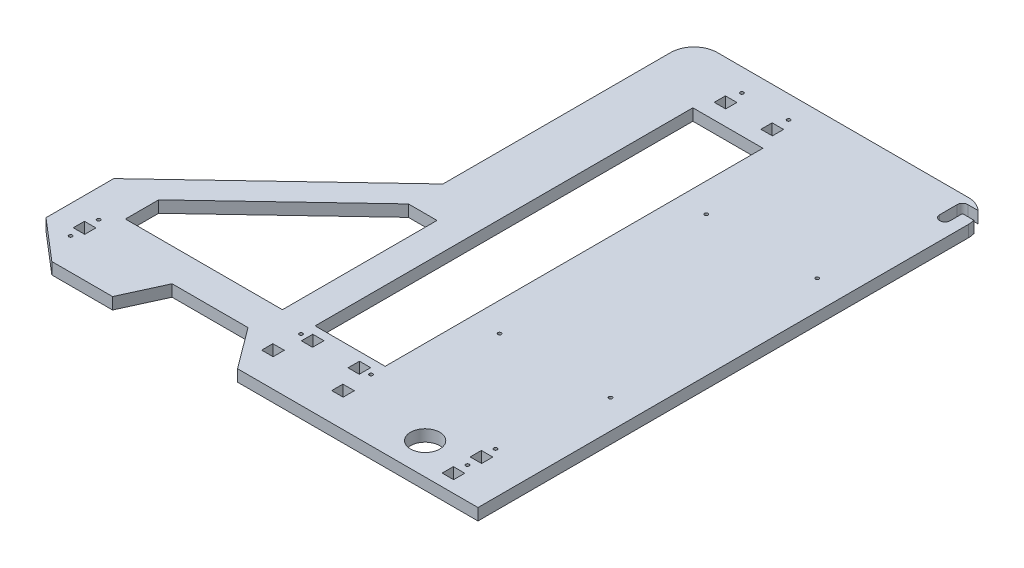
SolidWorks part; units mm, degrees
ref_plane "Front Plane" through (0, 0, 0) normal (0, 0, 1) x (1, 0, 0)
ref_plane "Top Plane" through (0, 0, 0) normal (0, 1, 0) x (1, 0, 0)
ref_plane "Right Plane" through (0, 0, 0) normal (1, 0, 0) x (0, 0, -1)
sketch "Sketch1" plane through (0, 0, 0) normal (0, 1, 0) x (1, 0, 0)
  line L0 (0, 0) -> (-235, 0)
  line L1 (-235, 0) -> (-235, -215)
  line L2 (-235, -215) -> (-380, -352)
  line L3 (-380, -352) -> (-380, -410)
  line L4 (-380, -410) -> (-345, -440)
  line L5 (-345, -440) -> (-293, -440)
  line L6 (-293, -440) -> (-277, -405)
  line L7 (-277, -405) -> (-212, -405)
  line L8 (-212, -405) -> (-185.9255, -440)
  line L9 (-185.9255, -440) -> (0, -440)
  line L10 (0, 0) -> (0, -440)
  line L12 (-293, -440) -> (-185.9255, -440) construction
  dimension "D3" = 235
  dimension "D5" = 58
  dimension "D13" = 190
  dimension "D7" = 35
  dimension "D2" = 126.686
  dimension "D11" = 65
  dimension "D15" = 52
  dimension "D12" = 30
  dimension "D10" = 35
  dimension "D14" = 16
  dimension "D6" = 380
  dimension "D4" = 440
extrude "Boss-Extrude1" add sketch "Sketch1" along normal blind 10
sketch "Sketch16" plane through (0, 10, 0) normal (0, 1, 0) x (1, 0, 0)
  line L0 (0, -440) -> (20, -440)
  line L1 (20, -440) -> (20, 0)
  line L2 (20, 0) -> (0, 0)
  line L3 (0, 0) -> (0, -440)
  dimension "D1" = 20
  dimension "D2" = 90
extrude "Boss-Extrude2" add sketch "Sketch16" against normal through all
sketch "Sketch2" plane through (0, 10, 0) normal (0, 1, 0) x (1, 0, 0)
  line L0 (-235, -215) -> (-235, -405) construction
  line L1 (-277, -405) -> (-212, -405) construction
  line L2 (-345, -440) -> (-345, -318.931) construction
  line L3 (-235, -215) -> (-380, -352) construction
  line L4 (-345, -348.5097) -> (-235, -244.5787)
  line L5 (-235, -244.5787) -> (-210.5, -244.5787)
  line L6 (-210.5, -244.5787) -> (-210.5, -377)
  line L7 (-210.5, -377) -> (-345, -377)
  line L8 (-345, -377) -> (-345, -348.5097)
  line L9 (0, -440) -> (0, 0) construction
  line L10 (-184.5, -375) -> (-124.5, -375)
  line L11 (-184.5, -375) -> (-184.5, -51.45)
  line L12 (-184.5, -51.45) -> (-124.5, -51.45)
  line L13 (-124.5, -375) -> (-124.5, -51.45)
  line L14 (-124.5, -387.1) -> (-184.5, -387.1) construction
  line L15 (-16, -440) -> (-16, 0) construction
  line L16 (20, 0) -> (-235, 0) construction
  line L17 (-355.95, -430.6143) -> (-355.95, -329.2769) construction
  line L18 (-20.9, -429.8) -> (-11.1, -429.8)
  line L19 (-20.9, -429.8) -> (-20.9, -420.2)
  line L20 (-20.9, -420.2) -> (-11.1, -420.2)
  line L21 (-11.1, -429.8) -> (-11.1, -420.2)
  line L22 (-20.9, -429.8) -> (-11.1, -420.2) construction
  line L23 (-20.9, -420.2) -> (-11.1, -429.8) construction
  line L24 (-20.9, -405.8) -> (-11.1, -405.8)
  line L25 (-20.9, -405.8) -> (-20.9, -396.2)
  line L26 (-20.9, -396.2) -> (-11.1, -396.2)
  line L27 (-11.1, -405.8) -> (-11.1, -396.2)
  line L28 (-20.9, -405.8) -> (-11.1, -396.2) construction
  line L29 (-20.9, -396.2) -> (-11.1, -405.8) construction
  line L30 (-380, -410) -> (-345, -440) construction
  line L32 (-351.05, -396.2) -> (-360.85, -396.2)
  line L33 (-351.05, -396.2) -> (-351.05, -405.8)
  line L34 (-351.05, -405.8) -> (-360.85, -405.8)
  line L35 (-360.85, -396.2) -> (-360.85, -405.8)
  line L36 (-351.05, -396.2) -> (-360.85, -405.8) construction
  line L37 (-351.05, -405.8) -> (-360.85, -396.2) construction
  line L38 (-185.9255, -440) -> (20, -440) construction
  line L39 (-185.9255, -440) -> (20, -440) construction
  line L40 (-173.724, -33.45) -> (-113.724, -33.45) construction
  line L41 (-154.5, -51.45) -> (-154.5, -33.45) construction
  line L42 (-179.4, -28.65) -> (-169.6, -28.65)
  line L43 (-179.4, -28.65) -> (-179.4, -38.25)
  line L44 (-179.4, -38.25) -> (-169.6, -38.25)
  line L45 (-169.6, -28.65) -> (-169.6, -38.25)
  line L46 (-179.4, -28.65) -> (-169.6, -38.25) construction
  line L47 (-179.4, -38.25) -> (-169.6, -28.65) construction
  line L48 (-129.6, -38.25) -> (-139.4, -28.65) construction
  line L49 (-129.6, -28.65) -> (-139.4, -38.25) construction
  line L50 (-139.4, -28.65) -> (-139.4, -38.25)
  line L51 (-129.6, -38.25) -> (-139.4, -38.25)
  line L52 (-129.6, -28.65) -> (-129.6, -38.25)
  line L53 (-129.6, -28.65) -> (-139.4, -28.65)
  line L54 (-174.5, -33.45) -> (-174.5, -19.45) construction
  line L55 (-134.5, -33.45) -> (-134.5, -19.45) construction
  line L56 (-154.5, -375) -> (-154.5, -440) construction
  line L57 (-174.5, -387.1) -> (-134.5, -387.1) construction
  line L58 (-129.7, -392) -> (-139.3, -382.2) construction
  line L59 (-179.3, -382.2) -> (-169.7, -382.2)
  line L60 (-179.3, -382.2) -> (-179.3, -392)
  line L61 (-179.3, -392) -> (-169.7, -392)
  line L62 (-169.7, -382.2) -> (-169.7, -392)
  line L63 (-179.3, -382.2) -> (-169.7, -392) construction
  line L64 (-179.3, -392) -> (-169.7, -382.2) construction
  line L65 (-129.7, -382.2) -> (-139.3, -392) construction
  line L66 (-139.3, -382.2) -> (-139.3, -392)
  line L67 (-129.7, -392) -> (-139.3, -392)
  line L68 (-129.7, -382.2) -> (-129.7, -392)
  line L69 (-129.7, -382.2) -> (-139.3, -382.2)
  line L70 (-119.6, -415.9) -> (-129.4, -406.3) construction
  line L71 (-189.4, -406.3) -> (-179.6, -406.3)
  line L72 (-189.4, -406.3) -> (-189.4, -415.9)
  line L73 (-189.4, -415.9) -> (-179.6, -415.9)
  line L74 (-179.6, -406.3) -> (-179.6, -415.9)
  line L75 (-189.4, -406.3) -> (-179.6, -415.9) construction
  line L76 (-189.4, -415.9) -> (-179.6, -406.3) construction
  line L77 (-119.6, -406.3) -> (-129.4, -415.9) construction
  line L78 (-129.4, -406.3) -> (-129.4, -415.9)
  line L79 (-119.6, -415.9) -> (-129.4, -415.9)
  line L80 (-119.6, -406.3) -> (-119.6, -415.9)
  line L81 (-119.6, -406.3) -> (-129.4, -406.3)
  line L82 (-360.85, -396.2) -> (-11.1, -396.2) construction
  circle A0 centre (-16, -413) radius 1.45
  circle A1 centre (-16, -389) radius 1.45
  circle A2 centre (-355.95, -413) radius 1.45
  circle A3 centre (-355.95, -389) radius 1.45
  circle A4 centre (-174.5, -19.45) radius 1.45
  circle A5 centre (-134.5, -19.45) radius 1.45
  circle A6 centre (-124.5, -387.1) radius 1.45
  circle A7 centre (-184.5, -387.1) radius 1.45
  point P25 (-16, -425)
  point P30 (-16, -401)
  point P44 (-355.95, -401)
  point P61 (-174.5, -33.45)
  point P72 (-134.5, -33.45)
  point P85 (-174.5, -387.1)
  point P94 (-134.5, -387.1)
  point P95 (-184.5, -411.1)
  point P104 (-124.5, -411.1)
  point P105 (-154.5, -387.1)
  dimension "D13" = 2.9
  dimension "D14" = 2.9
  dimension "D23" = 2.9
  dimension "D24" = 2.9
  dimension "D31" = 2.9
  dimension "D37" = 2.9
  dimension "D1" = 21.5
  dimension "D2" = 28
  dimension "D3" = 24.5
  dimension "D4" = 60
  dimension "D7" = 26
  dimension "D8" = 9.6
  dimension "D9" = 9.8
  dimension "D10" = 9.8
  dimension "D11" = 9.6
  dimension "D12" = 24
  dimension "D15" = 24
  dimension "D19" = 9.8
  dimension "D20" = 9.6
  dimension "D26" = 12
  dimension "D27" = 9.8
  dimension "D28" = 9.6
  dimension "D33" = 9.6
  dimension "D38" = 9.8
  dimension "D39" = 9.6
  dimension "D41" = 24
  dimension "D34" = 30
  dimension "D36" = 12.1
  dimension "D30" = 18
  dimension "D29" = 40
  dimension "D17" = 15
  dimension "D32" = 14
  dimension "D35" = 20
  dimension "D16" = 12
  dimension "D21" = 90
  dimension "D25" = 24
  dimension "D5" = 353.75
  dimension "D22" = 349.75
  dimension "D40" = 30
  dimension "D6" = 65
  dimension "D42" = 0
  dimension "D43" = 0
  dimension "D18" = 16
  dimension "D44" = 9.8
extrude "Cut-Extrude1" cut sketch "Sketch2" against normal through all
fillet "Fillet1" radius 20 2 edges at (-235, 5, 0) (20, 5, 0)
sketch "Sketch11" plane through (0, 10, 0) normal (0, 1, 0) x (1, 0, 0)
  line L0 (-124.5, -213.225) -> (20, -213.225) construction
  line L1 (20, -440) -> (20, -20) construction
  line L3 (-52.25, -213.225) -> (-52.25, -440) construction
  line L6 (-124.5, -375) -> (-124.5, -51.45) construction
  line L8 (-185.9255, -440) -> (20, -440) construction
  circle A0 centre (-52.25, -413) radius 12.5
  circle A1 centre (-16, -413) radius 1.45 construction
  dimension "D1" = 25
  dimension "D2" = 0
  dimension "D3" = 0
extrude "WiringHole" cut sketch "Sketch11" against normal through all
sketch "Sketch9" plane through (0, 10, 0) normal (0, 1, 0) x (1, 0, 0)
  line L0 (-52.25, -400.5) -> (-52.25, 0) construction
  line L1 (0, 0) -> (-215, 0) construction
  line L2 (-124.5, -213.225) -> (20, -213.225) construction
  line L3 (-124.5, -375) -> (-124.5, -51.45) construction
  line L4 (-4.75, -124.725) -> (-4.75, -301.725) construction
  line L6 (-99.75, -124.725) -> (-4.75, -124.725) construction
  line L7 (-4.75, -301.725) -> (-99.75, -301.725) construction
  line L8 (-99.75, -301.725) -> (-99.75, -124.725) construction
  line L9 (20, -440) -> (20, -20) construction
  circle A0 centre (-52.25, -413) radius 12.5 construction
  circle A1 centre (-99.75, -124.725) radius 1.45
  circle A2 centre (-4.75, -124.725) radius 1.45
  circle A3 centre (-4.75, -301.725) radius 1.45
  circle A4 centre (-99.75, -301.725) radius 1.45
  dimension "D3" = 2.9
  dimension "D4" = 2.9
  dimension "D1" = 95
  dimension "D2" = 177
  dimension "D5" = 47.5
extrude "MountingHoles-PSU" cut sketch "Sketch9" against normal through all
sketch "Sketch10" [suppressed] plane through (0, 10, 0) normal (0, 1, 0) x (1, 0, 0)
  line L0 (-124.5, -213.225) -> (20, -213.225) construction
  line L1 (20, -440) -> (20, -20) construction
  line L2 (-64.75, -228.225) -> (-39.75, -228.225) construction
  line L3 (-52.25, -213.225) -> (-52.25, 0) construction
  line L7 (-124.5, -375) -> (-124.5, -51.45) construction
  line L8 (-64.75, -278.225) -> (-39.75, -278.225)
  line L9 (-64.75, -278.225) -> (-64.75, -178.225)
  line L10 (-64.75, -178.225) -> (-39.75, -178.225)
  line L11 (-39.75, -278.225) -> (-39.75, -178.225)
  line L12 (-64.75, -278.225) -> (-39.75, -178.225) construction
  line L13 (-64.75, -178.225) -> (-39.75, -278.225) construction
  line L15 (0, 0) -> (-215, 0) construction
  line L17 (-52.25, -213.225) -> (-52.25, -440) construction
  line L18 (-185.9255, -440) -> (20, -440) construction
  line L19 (-64.75, -213.225) -> (-39.75, -213.225) construction
  line L20 (-52.25, -278.225) -> (-52.25, -178.225) construction
  dimension "D1" = 25
  dimension "D2" = 100
  dimension "D3" = 0
  dimension "D4" = 0
  dimension "D5" = 0
  dimension "D6" = 15
extrude "WiringSlot" [suppressed] cut sketch "Sketch10" against normal through all
sketch "CenterLines" [suppressed] plane through (0, 10, 0) normal (0, 1, 0) x (1, 0, 0)
  line L0 (-52.25, -278.225) -> (-52.25, -178.225) construction
  line L1 (-64.75, -278.225) -> (-39.75, -278.225) construction
  line L2 (-39.75, -178.225) -> (-64.75, -178.225) construction
  line L3 (-64.75, -228.225) -> (-39.75, -228.225) construction
  line L4 (-64.75, -178.225) -> (-64.75, -278.225) construction
  line L5 (-39.75, -278.225) -> (-39.75, -178.225) construction
ref_plane "Plane1" [suppressed] through (-52.25, 0, 0) normal (1, 0, 0) x (0, 0, -1)
sketch "Sketch6" [suppressed] plane through (0, 10, 0) normal (0, 1, 0) x (1, 0, 0)
  line L0 (-52.25, -278.225) -> (-52.25, -178.225) construction
  line L1 (-76.35, -237.075) -> (-28.15, -237.075) construction
  line L2 (-28.15, -192.625) -> (-28.15, -275.125) construction
  line L3 (-64.75, -278.225) -> (-39.75, -278.225) construction
  line L4 (-64.75, -245.925) -> (-39.75, -245.925) construction
  line L5 (-39.75, -178.225) -> (-64.75, -178.225) construction
  line L6 (-28.15, -192.625) -> (-28.15, -199.625) construction
  line L7 (-26.7, -192.625) -> (-26.7, -199.625)
  line L8 (-29.6, -192.625) -> (-29.6, -199.625)
  line L9 (-64.75, -228.225) -> (-39.75, -228.225) construction
  line L10 (-64.75, -178.225) -> (-64.75, -278.225) construction
  line L11 (-39.75, -278.225) -> (-39.75, -178.225) construction
  line L12 (-28.15, -282.125) -> (-28.15, -275.125) construction
  line L13 (-29.6, -282.125) -> (-29.6, -275.125)
  line L14 (-76.35, -274.525) -> (-76.35, -199.625) construction
  line L15 (-28.15, -282.125) -> (-28.15, -199.625) construction
  line L16 (-26.7, -282.125) -> (-26.7, -275.125)
  arc A2 (-26.7, -192.625) -> (-29.6, -192.625) centre (-28.15, -192.625) ccw
  arc A3 (-29.6, -199.625) -> (-26.7, -199.625) centre (-28.15, -199.625) ccw
  circle A4 centre (-76.35, -274.525) radius 1.45
  circle A6 centre (-76.35, -199.625) radius 1.45
  arc A8 (-29.6, -282.125) -> (-26.7, -282.125) centre (-28.15, -282.125) ccw
  arc A9 (-26.7, -275.125) -> (-29.6, -275.125) centre (-28.15, -275.125) ccw
  point P20 (-28.15, -196.125)
  point P25 (-28.15, -278.625)
  dimension "D8" = 2.9
  dimension "D12" = 2.9
  dimension "D4" = 1.45
  dimension "D5" = 1.45
  dimension "D11" = 82.5
  dimension "D14" = 74.9
  dimension "D2" = 24.1
  dimension "D3" = 48.2
  dimension "D6" = 8.85
  dimension "D9" = 7
  dimension "D10" = 7
extrude "MountingHoles-RAMPS" [suppressed] cut sketch "Sketch6" against normal through all
mirror "Mirror1" [suppressed] about plane through (-52.25, 0, 0) normal (1, 0, 0)
sketch "Sketch5" [suppressed] plane through (0, 10, 0) normal (0, 1, 0) x (1, 0, 0)
  line L0 (-39.75, -228.225) -> (-64.75, -228.225) construction
  line L3 (-39.75, -278.225) -> (-39.75, -178.225) construction
  line L5 (-64.75, -178.225) -> (-64.75, -278.225) construction
  line L7 (-31.25, -127.725) -> (-73.25, -127.725) construction
  line L8 (-31.25, -328.725) -> (-73.25, -328.725) construction
  line L9 (-52.25, -228.225) -> (-52.25, -127.725) construction
  line L10 (-52.25, -228.225) -> (-52.25, -328.725) construction
  circle A0 centre (-73.25, -127.725) radius 1.45
  circle A1 centre (-31.25, -127.725) radius 1.45
  circle A2 centre (-31.25, -328.725) radius 1.45
  circle A3 centre (-73.25, -328.725) radius 1.45
  point P17 (-52.25, -127.725)
  point P22 (-52.25, -328.725)
  dimension "D2" = 2.9
  dimension "D5" = 2.9
  dimension "D6" = 2.9
  dimension "D7" = 2.9
  dimension "D3" = 201
  dimension "D4" = 100.5
  dimension "D8" = 21
  dimension "D9" = 21
  dimension "D10" = 100.5
extrude "MountingHoles-Melzi" [suppressed] cut sketch "Sketch5" against normal through all
sketch "Sketch13" [suppressed] plane through (0, 0, 0) normal (0, -1, 0) x (-1, 0, 0)
  line L0 (64.75, -213.225) -> (124.5, -213.225) construction
  line L1 (124.5, -375) -> (124.5, -51.45) construction
  line L2 (101.46, -262.74) -> (101.46, -163.71) construction
  line L3 (52.25, -278.225) -> (52.25, -178.225) construction
  line L4 (64.75, -178.225) -> (64.75, -278.225) construction
  line L6 (101.46, -262.74) -> (3.56, -262.74) construction
  circle A0 centre (101.46, -163.71) radius 1.45
  circle A1 centre (101.46, -262.74) radius 1.45
  circle A2 centre (8.62, -170.19) radius 1.45
  circle A3 centre (3.56, -262.74) radius 1.45
  point P11 (101.46, -213.225)
  dimension "D8" = 2.9
  dimension "D6" = 2.9
  dimension "D1" = 2.9
  dimension "D2" = 49.515
  dimension "D3" = 49.21
  dimension "D4" = 6.48
  dimension "D5" = 92.84
  dimension "D7" = 97.9
extrude "Mountingholes-Smoothieboard" [suppressed] cut sketch "Sketch13" against normal through all
mirror "Flipped" [suppressed] about plane through (-52.25, 0, 0) normal (1, 0, 0)
sketch "Sketch21" [suppressed] plane through (0, 10, 0) normal (0, 1, 0) x (1, 0, 0)
  line L0 (-52.25, -178.225) -> (-52.25, 0) construction
  line L1 (-39.75, -178.225) -> (-64.75, -178.225) construction
  line L2 (0, 0) -> (-215, 0) construction
  line L3 (-52.25, -82.725) -> (-23.3697, -82.725) construction
  circle A0 centre (-27.75, -53.725) radius 1.45
  circle A1 centre (-76.75, -53.725) radius 1.45
  circle A2 centre (-76.75, -111.725) radius 1.45
  circle A3 centre (-27.75, -111.725) radius 1.45
  circle A4 centre (-31.25, -127.725) radius 1.45 construction
  dimension "D1" = 2.9
  dimension "D2" = 24.5
  dimension "D3" = 29
  dimension "D4" = 45
extrude "Pi" [suppressed] cut sketch "Sketch21" against normal through all
sketch "Sketch17" plane through (0, 10, 0) normal (0, 1, 0) x (1, 0, 0)
  line L0 (0, 0) -> (20, 0) construction
  line L1 (20, -23.6361) -> (20, 0) construction
  line L2 (20, -440) -> (20, -20) construction
  line L3 (20, -10) -> (5, -10) construction
  line L4 (20, -14.5) -> (5, -14.5)
  line L5 (20, -5.5) -> (5, -5.5)
  arc A0 (20, -14.5) -> (20, -5.5) centre (20, -10) ccw
  arc A1 (5, -5.5) -> (5, -14.5) centre (5, -10) ccw
  point P8 (12.5, -10)
  dimension "D1" = 9
  dimension "D2" = 15
  dimension "D3" = 10
extrude "Cut-Extrude3" cut sketch "Sketch17" against normal through all
sketch "Sketch18" plane through (0, 10, 0) normal (0, 1, 0) x (1, 0, 0)
  line L0 (5, -5.5) -> (5, -14.5) construction
  line L1 (0.5, -10) -> (5, -10) construction
  line L2 (5, -10) -> (5, -25) construction
  line L3 (9.5, -10) -> (9.5, -25)
  line L4 (0.5, -10) -> (0.5, -25)
  arc A0 (5, -5.5) -> (5, -14.5) centre (5, -10) ccw construction
  arc A1 (9.5, -10) -> (0.5, -10) centre (5, -10) ccw
  arc A2 (0.5, -25) -> (9.5, -25) centre (5, -25) ccw
  point P10 (5, -17.5)
  dimension "D1" = 9
  dimension "D2" = 0
  dimension "D3" = 15
extrude "Cut-Extrude4" cut sketch "Sketch18" against normal through all
sketch "Sketch19" plane through (0, 10, 0) normal (0, 1, 0) x (1, 0, 0)
  line L0 (-5, -25) -> (15, -25) construction
  line L1 (5, -25) -> (5, -5.5) construction
  circle A0 centre (15, -25) radius 1.45
  arc A1 (5, -5.5) -> (0.5, -10) centre (5, -10) ccw construction
  circle A2 centre (-5, -25) radius 1.45
  dimension "D2" = 2.9
extrude "Cut-Extrude5" [suppressed] cut sketch "Sketch19" against normal through all
equation "\"Y-ROD-SPACING\"=75"
equation "\"Y-BED-OFFSET\"=2"
equation "\"Y-BED-ROD-INSET\"=3.5"
equation "\"T-SLOT-NUT-FILLET-RADIUS\"=0.5"
equation "\"T-SLOT-SCREW-SHAFT-RADIUS\"=1.55"
equation "\"T-SLOT-SCREW-SHAFT-CUTOUT-LENGTH\"=11.0"
equation "\"T-SLOT-NUT-DEPTH\"=3.5"
equation "\"T-SLOT-NUT-WIDTH\"=2.85"
equation "\"T-SLOT-NUT-END-DISTANCE\"=8"
equation "\"ACRYLIC-TAB-CUTOUT-SIZE\"=\"ACRYLIC-THICKNESS\"+\"ACRYLIC-TAB-TOLERANCE\"*2"
equation "\"ACRYLIC-TAB-WIDTH\"=\"ACRYLIC-THICKNESS\""
equation "\"ACRYLIC-M3-HOLE\"=2.9"
equation "\"SMOOTHROD-CAP-SCREW-DISTANCE\"=20"
equation "\"FRAME-WIDTH-INNER\"=370"
equation "\"D24@Sketch2\"=\"ACRYLIC-M3-HOLE\""
equation "\"D23@Sketch2\"=\"ACRYLIC-M3-HOLE\""
equation "\"D19@Sketch2\"=\"ACRYLIC-THICKNESS\"-\"KERF\"*2"
equation "\"D20@Sketch2\"=\"ACRYLIC-TAB-WIDTH\"-\"KERF\"*4"
equation "\"D37@Sketch2\"=\"ACRYLIC-M3-HOLE\""
equation "\"D33@Sketch2\"=\"ACRYLIC-TAB-WIDTH\"-\"KERF\"*4"
equation "\"D38@Sketch2\"=\"ACRYLIC-THICKNESS\"-\"KERF\"*2"
equation "\"D39@Sketch2\"=\"ACRYLIC-TAB-WIDTH\"-\"KERF\"*4"
equation "\"D13@Sketch2\"=\"ACRYLIC-M3-HOLE\""
equation "\"D14@Sketch2\"=\"ACRYLIC-M3-HOLE\""
equation "\"D8@Sketch2\"=\"ACRYLIC-TAB-WIDTH\"-\"KERF\"*4"
equation "\"D9@Sketch2\"=\"ACRYLIC-THICKNESS\"-\"KERF\"*2"
equation "\"D10@Sketch2\"=\"ACRYLIC-THICKNESS\"-\"KERF\"*2"
equation "\"D11@Sketch2\"=\"ACRYLIC-TAB-WIDTH\"-\"KERF\"*4"
equation "\"D31@Sketch2\"=\"ACRYLIC-M3-HOLE\""
equation "\"D27@Sketch2\"=\"ACRYLIC-THICKNESS\"-\"KERF\"*2"
equation "\"D28@Sketch2\"=\"ACRYLIC-TAB-WIDTH\"-\"KERF\"*4"
equation "\"NEMA17-HOLE-SPACING\"=31"
equation "\"NEMA17-CENTRAL-CUTOUT\"=22.5"
equation "\"Z-BRACKET-REACH\"=55"
equation "\"TOP-BRACKET-SPACING\"=40"
equation "\"D29@Sketch2\"=\"TOP-BRACKET-SPACING\""
equation "\"ACRYLIC-THICKNESS\"=10"
equation "\"SMOOTHROD-Z-LENGTH\"=350"
equation "\"D5@Sketch2\"=\"SMOOTHROD-Z-LENGTH\"-\"SMOOTHROD-TIGHTENING-HEADROOM\"+4"
equation "\"SMOOTHROD-X-LENGTH\"=350"
equation "\"SMOOTHROD-Y-LENGTH\"=350"
equation "\"D22@Sketch2\"=\"SMOOTHROD-Y-LENGTH\"-\"SMOOTHROD-TIGHTENING-HEADROOM\""
equation "\"SMOOTHROD-TIGHTENING-HEADROOM\"=.25"
equation "\"X-ROD-SPACING\"=45"
equation "\"Z-ROD-SPACING\"=17.5"
equation "\"LEADSCREW-Z-LENGTH\"=300"
equation "\"SCREW-HEAD-RADIUS\"=6"
equation "\"PRINTED-X-SMOOTHROD-DIAMETER\"=9.0"
equation "\"PRINTED-X-SMOOTHROD-CUTOUT\"=10"
equation "\"PRINTED-X-BASE-HEIGHT\"=10"
equation "\"PRINTED-LM8UU-CUTOUT-SIZE\"=15.5"
equation "\"PRINTED-LM8UU-CUTOUT-LENGTH\"=24.5"
equation "\"PRINTED-X-IDLER-HEIGHT\"=16"
equation "\"PSU-MOUNTING-WIDTH\"=95"
equation "\"PSU-MOUNTING-HEIGHT\"=177"
equation "\"D1@Sketch9\"=\"PSU-MOUNTING-WIDTH\""
equation "\"D3@Sketch9\"=\"ACRYLIC-M3-HOLE\""
equation "\"D1@Boss-Extrude1\"=\"ACRYLIC-THICKNESS\""
equation "\"D6@Sketch1\"=\"SMOOTHROD-Y-LENGTH\"+30"
equation "\"D4@Sketch9\"=\"ACRYLIC-M3-HOLE\""
equation "\"D2@Sketch9\"=\"PSU-MOUNTING-HEIGHT\""
equation "\"D5@Sketch9\"=\"PSU-MOUNTING-WIDTH\"/2"
equation "\"D4@Sketch1\"=\"SMOOTHROD-Z-LENGTH\"+90"
equation "\"D8@Sketch6\"=\"ACRYLIC-M3-HOLE\""
equation "\"D12@Sketch6\"=\"ACRYLIC-M3-HOLE\""
equation "\"D2@Sketch5\"=\"ACRYLIC-M3-HOLE\""
equation "\"D5@Sketch5\"=\"ACRYLIC-M3-HOLE\""
equation "\"D6@Sketch5\"=\"ACRYLIC-M3-HOLE\""
equation "\"D7@Sketch5\"=\"ACRYLIC-M3-HOLE\""
equation "\"D1@Sketch13\"=\"ACRYLIC-M3-HOLE\""
equation "\"D6@Sketch13\"=\"ACRYLIC-M3-HOLE\""
equation "\"D8@Sketch13\"=\"ACRYLIC-M3-HOLE\""
equation "\"D4@Sketch6\"=\"ACRYLIC-M3-HOLE\"/2"
equation "\"D5@Sketch6\"=\"ACRYLIC-M3-HOLE\"/2"
equation "\"Y-BED-SCREW-SPACING\"=209"
equation "\"Y-BED-SCREW-CUTOUT-SLOT-HEIGHT\"=2"
equation "\"ACRYLIC-THICKNESS2\"=4.5"
equation "\"ACRYLIC-TAB-TOLERANCE\"=-.05"
equation "\"Z-ROD-INSET\"=16"
equation "\"SCREW-LENGTH-FRAME\"=\"ACRYLIC-THICKNESS\" + 10"
equation "\"SCREW-LENGTH-MOTOR\"=\"ACRYLIC-THICKNESS\" + 5"
equation "\"SCREW-LENGTH-EXTRUDER\"=28"
equation "\"Y-BELT-TO-ROD-DISTANCE\"=20"
equation "\"SPOOL-HOLDER-ROD-SPACING\"=150"
equation "\"ACRYLIC-X-CARRIAGE-WIDTH\"=55"
equation "\"ACRYLIC-X-CARRIAGE-HEIGHT\"=75"
equation "\"ACRYLIC-X-CARRIAGE-LM8UU-CUTOUT-WIDTH\"=24.25"
equation "\"ACRYLIC-X-CARRIAGE-SCREW-SPACING-X\"=15"
equation "\"ACRYLIC-X-CARRIAGE-SCREW-SPACING-Y\"=33"
equation "\"ACRYLIC-X-CARRIAGE-CENTER-TAB-SPACING\"=14"
equation "\"ACRYLIC-X-CARRIAGE-EXTRUDER-OFFSET\"=26"
equation "\"ACRYLIC-X-CARRIAGE-EXTRUDER-ANGLE\"=90"
equation "\"ACRYLIC-X-CARRIAGE-EXTRUDER-SHELF-DEPTH\"=\"ACRYLIC-X-CARRIAGE-EXTRUDER-OFFSET\" + 28"
equation "\"ACRYLIC-X-CARRIAGE-EXTRUDER-BRACE-SPACING\"=23"
equation "\"ACRYLIC-X-CARRIAGE-EXTRUDER-BRACE-TAB-OFFSET\"=20"
equation "\"ACRYLIC-X-CARRIAGE-EXTRUDER-BRACE-HEIGHT\"=35"
equation "\"ACRYLIC-X-CARRIAGE-EXTRUDER-BRACE-SCREW-SPACING\"=22"
equation "\"D1@Sketch19\"=\"SMOOTHROD-CAP-SCREW-DISTANCE\"/2"
equation "\"D2@Sketch19\"=\"ACRYLIC-M3-HOLE\""
equation "\"D1@Sketch21\"=\"ACRYLIC-M3-HOLE\""
equation "\"KERF\"=0.1"
equation "\"PRINTED-M3-HOLE\"=3.5"
equation "\"PRINTED-M3-NUT-AF\"=6.25"
equation "\"ACRYLIC-X-CARRIAGE-LM8UU-CUTOUT-HEIGHT\"=11.0"
equation "\"ACRYLIC-X-CARRIAGE-DUAL-WIDTH-MULTIPLIER\"=1.65"
equation "\"ACRYLIC-X-CARRIAGE-DUAL-HOTEND-SPACING\"=42"
equation "\"ACRYLIC-X-CARRIAGE-DUAL-WIDTH\"=75"
equation "\"ACRYLIC-X-CARRIAGE-DUAL-FAN-OFFSET\"=52"
equation "\"ACRYLIC-X-CARRIAGE-DUAL-FAN-HEIGHT\"=20"
equation "\"ACRYLIC-X-CARRIAGE-DUAL-HOTEND-SEPARATION\"=36"
equation "\"ACRYLIC-X-CARRIAGE-DUAL-MOUNT-PLATE-DEPTH\"=75"
equation "\"ACRYLIC-X-CARRIAGE-DUAL-MOUNT-BRACE-WIDTH\"=33"
equation "\"ACRYLIC-X-CARRIAGE-DUAL-MOUNT-SCREW-WIDTH\"=40"
equation "\"BLOWER-FAN-WIDTH\"=15"
equation "\"D44@Sketch2\"=\"ACRYLIC-THICKNESS\"-\"KERF\"*2"
